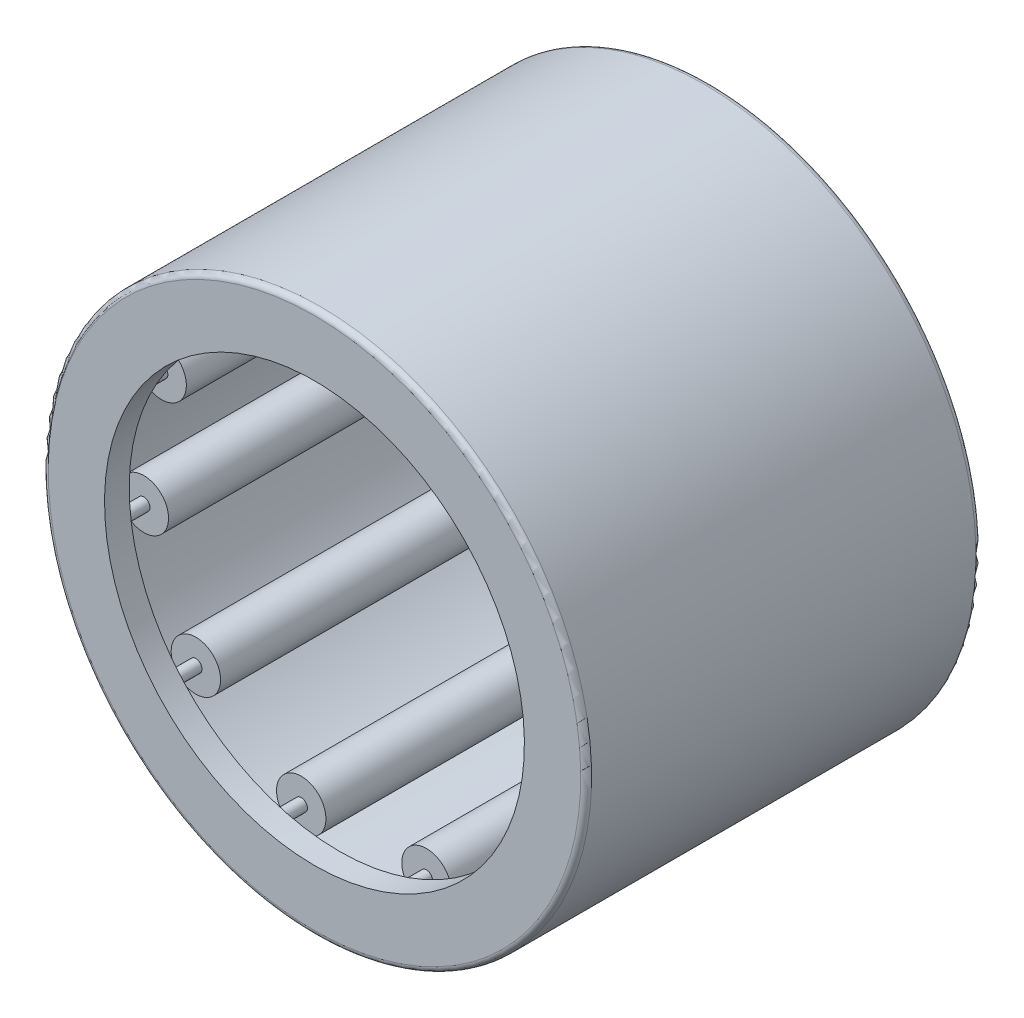
SolidWorks part; units mm, degrees
ref_plane "Front Plane" through (0, 0, 0) normal (0, 0, 1) x (1, 0, 0)
ref_plane "Top Plane" through (0, 0, 0) normal (0, 1, 0) x (1, 0, 0)
ref_plane "Right Plane" through (0, 0, 0) normal (1, 0, 0) x (0, 0, -1)
sketch "Sketch1" plane through (0, 0, 0) normal (1, 0, 0) x (0, 0, -1)
  line L0 (-6.35, 0) -> (6.35, 0) construction
  line L1 (0, 0) -> (0, 8.7312) construction
  line L2 (-6.35, 0) -> (-6.35, 8.7312) construction
  line L3 (-6.35, 8.7312) -> (6.35, 8.7312)
  line L4 (6.35, 8.7312) -> (6.35, 0) construction
  line L5 (6.35, 0) -> (5.5562, 0) construction
  line L6 (5.5562, 0) -> (5.5563, 7.9375) construction
  line L7 (5.5563, 7.9375) -> (-5.5563, 7.9375)
  line L8 (-5.5563, 7.9375) -> (-5.5562, 0) construction
  line L9 (-5.5562, 0) -> (-6.35, 0) construction
  line L10 (-6.35, 8.7312) -> (-6.35, 6.7469)
  line L11 (-6.35, 6.7469) -> (-5.5562, 6.7469)
  line L12 (-5.5562, 6.7469) -> (-5.5563, 7.9375)
  line L13 (5.5563, 8.7313) -> (5.5563, 7.9375) construction
  line L14 (5.5563, 7.9375) -> (5.5562, 6.7469)
  line L15 (5.5562, 6.7469) -> (6.35, 6.7469)
  line L16 (6.35, 6.7469) -> (6.35, 8.7312)
  line L17 (5.5563, 7.9375) -> (5.5563, 7.1438) construction
  line L18 (5.5563, 7.1438) -> (5.5563, 6.35) construction
  point P5 (0, 6.35)
  dimension "Width" = 12.7
  dimension "OD" = 17.4625
  dimension "Shaft Dia" = 12.7
revolve "Revolve1" add sketch "Sketch1" angle 360 about L0
sketch "Sketch2" plane through (0, 0, 0) normal (1, 0, 0) x (0, 0, -1)
  line L0 (5.5563, 7.9375) -> (-5.5563, 7.9375) construction
  line L1 (-4.7625, 7.1438) -> (4.7625, 7.1438) construction
  line L2 (-4.7625, 7.1438) -> (-4.7625, 7.9375) construction
  line L3 (-4.7625, 7.9375) -> (4.7625, 7.9375)
  line L4 (4.7625, 7.1438) -> (4.7625, 7.9375) construction
  line L5 (5.5562, 6.7469) -> (6.35, 6.7469) construction
  line L6 (-5.5562, 7.1437) -> (-4.7625, 7.1438) construction
  line L7 (4.7625, 7.1438) -> (5.5562, 7.1438) construction
  line L8 (-6.35, 6.7469) -> (-5.5562, 6.7469) construction
  line L9 (-4.7625, 7.3422) -> (-4.7625, 6.9453) construction
  line L10 (-5.5562, 7.1437) -> (-5.5562, 6.7469) construction
  line L11 (-4.7625, 7.9375) -> (-4.7625, 7.3422)
  line L12 (4.7625, 7.9375) -> (4.7625, 7.3422)
  line L13 (4.7625, 7.3422) -> (-4.7625, 7.3422)
  line L14 (0, 7.9375) -> (0, 6.35) construction
  line L15 (-5.5562, 6.7469) -> (-5.5562, 7.9375) construction
  line L16 (-4.7625, 6.9453) -> (-5.5563, 6.9453) construction
  line L17 (0, 0) -> (6.35, 0) construction
  line L31 (6.35, -8.7313) -> (6.35, 8.7312) construction
  point P16 (0, 7.1437)
revolve "Revolve2" add sketch "Sketch2" angle 360 about L1
sketch "Sketch3" plane through (0, 0, 0) normal (1, 0, 0) x (0, 0, -1)
  line L0 (5.5563, 7.9375) -> (5.5563, 6.7469) construction
  line L1 (-5.5562, 7.1437) -> (5.5563, 7.1437)
  line L2 (-5.5562, 7.1437) -> (-5.5562, 7.3422)
  line L3 (-5.5562, 7.3422) -> (5.5563, 7.3422)
  line L4 (5.5563, 7.1437) -> (5.5563, 7.3422)
  line L5 (0, 0) -> (6.35, 0) construction
  line L6 (6.35, -8.7313) -> (6.35, 8.7312) construction
revolve "Revolve3" add sketch "Sketch3" angle 360 about L1
ref_axis "Axis1" through (0, 0, -6.35) along (0, 0, 1)
pattern_circular "CirPattern1" count 11 every 32.727 about axis through (0, 0, -6.35) along (0, 0, 1) of bodies 166 167
fillet "Fillet1" radius 0.1746 2 edges at (0, -8.7313, -6.35) (0, -8.7312, 6.35)
sketch "Sketch4" plane through (0, 0, 0) normal (1, 0, 0) x (0, 0, -1)
  line L1 (6.1754, 6.35) -> (4.7625, 6.35)
  line L2 (6.1754, 6.35) -> (6.1754, 6.7469)
  line L3 (6.1754, 6.7469) -> (4.7625, 6.7469)
  line L4 (4.7625, 6.35) -> (4.7625, 6.7469)
  line L5 (-6.35, 6.7469) -> (-5.5562, 6.7469) construction
  line L6 (6.1754, -8.7313) -> (6.1754, 8.7312) construction
  line L7 (4.7625, 7.9375) -> (4.7625, 7.3422) construction
revolve "Revolve4" [suppressed] add sketch "Sketch4" angle 360 about L0
sketch "Sketch5" plane through (0, 0, 0) normal (1, 0, 0) x (0, 0, -1)
  line L0 (-6.1754, 8.7312) -> (-6.1754, -8.7312) construction
  line L1 (-4.7625, 6.35) -> (-6.1754, 6.35)
  line L2 (-4.7625, 6.35) -> (-4.7625, 6.7469)
  line L3 (-4.7625, 6.7469) -> (-6.1754, 6.7469)
  line L4 (-6.1754, 6.35) -> (-6.1754, 6.7469)
  line L6 (-4.7625, 7.9375) -> (-4.7625, 7.3422) construction
  line L7 (-6.35, 6.7469) -> (-5.5562, 6.7469) construction
revolve "Revolve5" [suppressed] add sketch "Sketch5" angle 360 about L0
sketch "Front View" plane through (0, 0, 0) normal (0, 0, 1) x (1, 0, 0)
  circle A0 centre (0, 0) radius 6.35 construction
  circle A1 centre (0, 0) radius 8.7312 construction
  dimension "OD" = 17.4625
  dimension "ID" = 12.7
sketch "Right View" plane through (0, 0, 0) normal (1, 0, 0) x (0, 0, -1)
  line L0 (-6.35, 8.7312) -> (6.35, 8.7312) construction
  dimension "Width" = 12.7
ref_axis "Center Axis 1" through (0, 0, -6.1754) along (0, 0, 1)
ref_plane "Contact Plane 1" through (0, 0, 6.35) normal (0, 0, 1) x (1, 0, 0)
ref_plane "Contact Plane 2" through (0, 0, -6.35) normal (0, 0, -1) x (-1, 0, 0)
equation "\"Rollers@CirPattern1\" = \"OD@Sketch1\"*16"
equation "\"D1@Fillet1\" = \"OD@Sketch1\"*.01"
equation "\"Angle@CirPattern1\"= 360 / \"Rollers@CirPattern1\""
equation "\"OD@Front View\"=\"OD@Sketch1\""
equation "\"ID@Front View\"=\"Shaft Dia@Sketch1\""
equation "\"Width@Right View\"=\"Width@Sketch1\""
